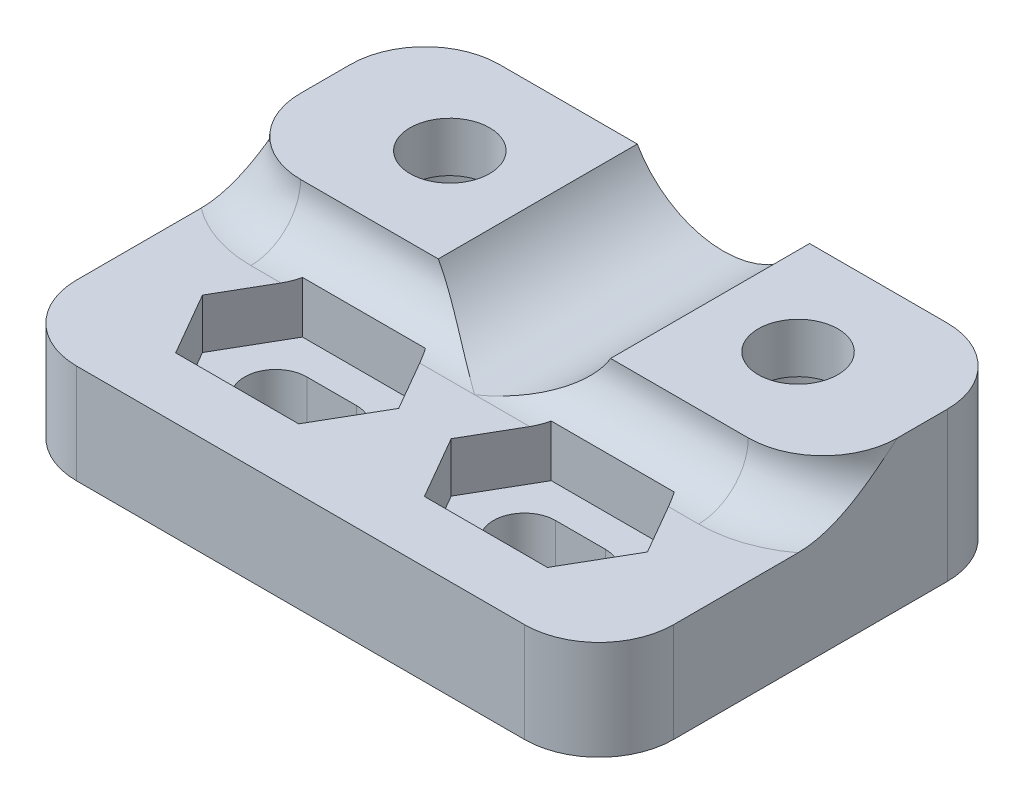
SolidWorks part; units mm, degrees
material "ABS"
ref_plane "Front Plane" through (0, 0, 0) normal (0, 0, 1) x (1, 0, 0)
ref_plane "Top Plane" through (0, 0, 0) normal (0, 1, 0) x (1, 0, 0)
ref_plane "Right Plane" through (0, 0, 0) normal (1, 0, 0) x (0, 0, -1)
sketch "Sketch1" plane through (0, 0, 0) normal (0, 1, 0) x (1, 0, 0)
  line L0 (-12, -5) -> (12, -5)
  line L1 (12, -5) -> (12, 12)
  line L2 (12, 12) -> (-12, 12)
  line L3 (-12, 12) -> (-12, -5)
  line L4 (-6, 0) -> (-4, 0) construction
  line L5 (-6, 1.25) -> (-4, 1.25)
  line L6 (-6, -1.25) -> (-4, -1.25)
  line L7 (4, 0) -> (6, 0) construction
  line L8 (4, 1.25) -> (6, 1.25)
  line L9 (4, -1.25) -> (6, -1.25)
  arc A2 (-6, 1.25) -> (-6, -1.25) centre (-6, 0) ccw
  arc A3 (-4, -1.25) -> (-4, 1.25) centre (-4, 0) ccw
  arc A4 (4, 1.25) -> (4, -1.25) centre (4, 0) ccw
  arc A5 (6, -1.25) -> (6, 1.25) centre (6, 0) ccw
  point P2 (-5, 0)
  point P9 (0, -5)
  point P13 (5, 0)
  dimension "D1" = 1.25
  dimension "D3" = 8
  dimension "D4" = 12
  dimension "D2" = 4
  dimension "D5" = 24
  dimension "D6" = 5
  dimension "D7" = 12
extrude "Boss-Extrude1" add sketch "Sketch1" along normal blind 4
sketch "Sketch2" plane through (0, 4, 0) normal (0, 1, 0) x (1, 0, 0)
  line L1 (-3.0555, 0) -> (-4.5278, 2.55)
  line L2 (-4.5278, 2.55) -> (-7.4722, 2.55)
  line L3 (-7.4722, 2.55) -> (-8.9445, 0)
  line L4 (-8.9445, 0) -> (-7.4722, -2.55)
  line L5 (-7.4722, -2.55) -> (-4.5278, -2.55)
  line L6 (-4.5278, -2.55) -> (-3.0555, 0)
  line L7 (-1.0555, 0) -> (-2.5278, 2.55)
  line L8 (-2.5278, 2.55) -> (-5.4722, 2.55)
  line L9 (-5.4722, 2.55) -> (-6.9445, 0)
  line L10 (-6.9445, 0) -> (-5.4722, -2.55)
  line L11 (-5.4722, -2.55) -> (-2.5278, -2.55)
  line L12 (-2.5278, -2.55) -> (-1.0555, 0)
  line L13 (1.0555, 0) -> (2.5278, -2.55)
  line L14 (2.5278, -2.55) -> (5.4722, -2.55)
  line L15 (5.4722, -2.55) -> (6.9445, 0)
  line L16 (6.9445, 0) -> (5.4722, 2.55)
  line L17 (5.4722, 2.55) -> (2.5278, 2.55)
  line L18 (2.5278, 2.55) -> (1.0555, 0)
  line L19 (8.9445, 0) -> (7.4722, 2.55)
  line L20 (7.4722, 2.55) -> (4.5278, 2.55)
  line L21 (4.5278, 2.55) -> (3.0555, 0)
  line L22 (3.0555, 0) -> (4.5278, -2.55)
  line L23 (4.5278, -2.55) -> (7.4722, -2.55)
  line L24 (7.4722, -2.55) -> (8.9445, 0)
  circle A0 centre (-6, 0) radius 2.55 construction
  circle A1 centre (-4, 0) radius 2.55 construction
  circle A2 centre (4, 0) radius 2.55 construction
  circle A3 centre (6, 0) radius 2.55 construction
  line M29 (-4, -1.25) -> (-6, -1.25)
  arc M30 (-6, -1.25) -> (-6, 1.25) centre (-6, 0) cw
  line M31 (-6, 1.25) -> (-4, 1.25)
  arc M32 (-4, 1.25) -> (-4, -1.25) centre (-4, 0) cw
  line M33 (6, -1.25) -> (4, -1.25)
  arc M34 (4, -1.25) -> (4, 1.25) centre (4, 0) cw
  line M35 (4, 1.25) -> (6, 1.25)
  arc M36 (6, 1.25) -> (6, -1.25) centre (6, 0) cw
  dimension "D1" = 5.1
extrude "Cut-Extrude1" cut sketch "Sketch2" against normal blind 2 contours L10 L9 L2 L3 L4 L5 M30 | L2 L9 L1 M30 M31 M32 | L10 L5 L6 M30 M32 M29 | L11 L12 L7 L8 L1 L6 M32 | L22 L21 L17 L18 L13 L14 M34 | L17 L21 L16 M34 M35 M36 | L23 L24 L19 L20 L16 L15 M36 | L22 L14 L15 M34 M36 M33 region at (-5, 4, -1.8032) region at (-2.7499, 4, 0) region at (-5, 4, 1.8032) region at (-7.2501, 4, 0) region at (2.7499, 4, 0) region at (5, 4, 1.8032) region at (5, 4, -1.8032) region at (7.2501, 4, 0)
sketch "Sketch3" plane through (0, 0, -12) normal (0, 0, -1) x (-1, 0, 0)
  line L0 (-12, 4) -> (12, 4) construction
  line L1 (12, 8) -> (-12, 8)
  line L2 (-12, 8) -> (-12, 4)
  line L3 (-12, 4) -> (12, 4)
  line L4 (12, 4) -> (12, 8)
  circle A0 centre (0, 8) radius 4
  point P7 (0, 8)
  line M8 (12, 4) -> (-12, 4)
  dimension "D1" = 8
  dimension "D2" = 24
extrude "Boss-Extrude2" add sketch "Sketch3" against normal blind 8 contours A0 L4 L1 M8 | A0 L1 L2 L3 region at (-7.5258, 5.8928, -12) region at (7.5258, 5.8928, -12)
sketch "Sketch4" plane through (0, 8, 0) normal (0, 1, 0) x (1, 0, 0)
  line L2 (4, 4) -> (4, 12) construction
  circle A0 centre (-7, 8) radius 1.6
  circle A1 centre (7, 8) radius 1.6
  point P15 (4, 8)
  dimension "D1" = 3.2
  dimension "D2" = 14
  dimension "D3" = 7
extrude "Cut-Extrude2" cut sketch "Sketch4" against normal up to next
sketch "Sketch5" plane through (0, 0, 0) normal (0, -1, 0) x (1, 0, 0)
  circle A3 centre (-7, -8) radius 3.1
  circle A4 centre (7, -8) radius 3.1
  dimension "D1" = 6.2
extrude "Cut-Extrude3" cut sketch "Sketch5" against normal blind 4
sketch "Sketch6" plane through (0, 0, -12) normal (0, 0, -1) x (-1, 0, 0)
  line L1 (-12, 8) -> (12, 8)
  line L2 (-12, 8) -> (-12, 6)
  line L3 (-12, 6) -> (12, 6)
  line L4 (12, 8) -> (12, 6)
  line L5 (12, 8) -> (12, 0) construction
  point P7 (-11.4141, 7.5073)
  dimension "D1" = 2
extrude "Cut-Extrude4" cut sketch "Sketch6" against normal blind 10
fillet "Fillet1" radius 3 6 edges at (12, 3, -12) (12, 2, 5) (12, 5, -4) (-12, 2, 5) (-12, 3, -12) (-12, 5, -4)
fillet "Fillet2" radius 2 4 edges at (-11.1213, 4, -4.8787) (11.1213, 4, -4.8787) (4.5, 4, -4) (-4.5, 4, -4)
equation "\"D2@Sketch1\"=\"D3@Sketch1\"/2"
equation "\"D3@Sketch4\"=\"D2@Sketch4\"/2"
